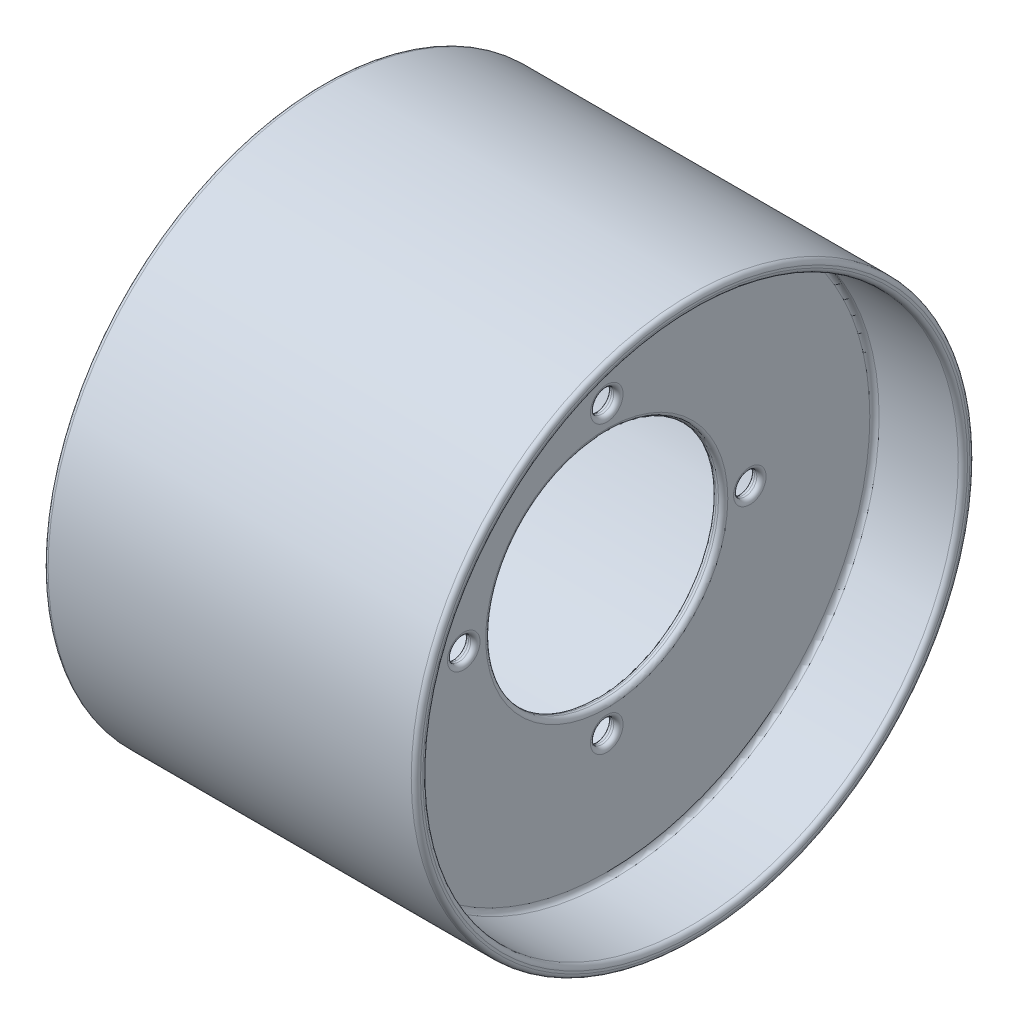
SolidWorks part; units mm, degrees
material "6061-T6 (SS)"
ref_plane "Front Plane" through (0, 0, 0) normal (0, 0, 1) x (1, 0, 0)
ref_plane "Top Plane" through (0, 0, 0) normal (0, 1, 0) x (1, 0, 0)
ref_plane "Right Plane" through (0, 0, 0) normal (1, 0, 0) x (0, 0, -1)
sketch "Sketch1" plane through (0, 0, 0) normal (1, 0, 0) x (0, 0, -1)
  circle A0 centre (0, 0) radius 152.4
  circle A1 centre (0, 0) radius 146.05
  dimension "D1" = 304.8
  dimension "D2" = 292.1
extrude "Boss-Extrude1" add sketch "Sketch1" along normal blind 203.2
fillet "Fillet3" radius 2.54 2 edges at (203.2, 0, -152.4) (203.2, 0, -146.05)
fillet "Fillet4" radius 2.54 2 edges at (0, 0, -152.4) (0, 0, -146.05)
ref_plane "Plane1" through (152.4, 0, 0) normal (1, 0, 0) x (0, 0, -1)
sketch "Sketch2" plane through (152.4, 0, 0) normal (1, 0, 0) x (0, 0, -1)
  circle A0 centre (0, 0) radius 146.05
  dimension "D1" = 292.1
extrude "Boss-Extrude2" add sketch "Sketch2" along normal blind 2.54 and the other way blind 3.81
fillet "Fillet5" radius 2.54 1 edges at (148.59, 0, -146.05)
fillet "Fillet6" radius 2.54 1 edges at (154.94, 0, -146.05)
sketch "Sketch3" plane through (152.4, 0, 0) normal (1, 0, 0) x (0, 0, -1)
  line L1 (-78.0415, 0) -> (0, -78.0415) construction
  line L2 (-78.0415, 0) -> (0, 78.0415) construction
  line L3 (0, 78.0415) -> (78.0415, 0) construction
  line L4 (0, -78.0415) -> (78.0415, 0) construction
  line L5 (-78.0415, 0) -> (78.0415, 0) construction
  line L6 (0, 78.0415) -> (0, -78.0415) construction
  circle A0 centre (0, 78.0415) radius 6.35
  circle A1 centre (0, -78.0415) radius 6.35
  circle A2 centre (78.0415, 0) radius 6.35
  circle A3 centre (-78.0415, 0) radius 6.35
  point P8 (0, 0)
  point P9 (0, -55.0311)
  point P12 (61.4101, 32.9471)
  point P15 (-47.3696, 78.486)
  point P16 (0, 62.8083)
  point P17 (0, 76.3974)
  dimension "D1" = 12.7
  dimension "D2" = 12.7
  dimension "D3" = 12.7
  dimension "D4" = 12.7
  dimension "D5" = 78.0415
extrude "Cut-Extrude1" cut sketch "Sketch3" against normal through all and the other way through all
sketch "Sketch4" plane through (152.4, 0, 0) normal (1, 0, 0) x (0, 0, -1)
  circle A0 centre (0, 0) radius 63.5
extrude "Cut-Extrude3" cut sketch "Sketch4" against normal through all and the other way through all
fillet "Fillet7" radius 2.54 5 edges at (154.94, 0, -63.5) (154.94, 0, 71.6915) (154.94, -78.0415, -6.35) (154.94, 0, -84.3915) (154.94, 78.0415, -6.35)
fillet "Fillet8" radius 2.54 5 edges at (148.59, 0, -84.3915) (148.59, -78.0415, -6.35) (148.59, 0, 71.6915) (148.59, 0, -63.5) (148.59, 78.0415, -6.35)
